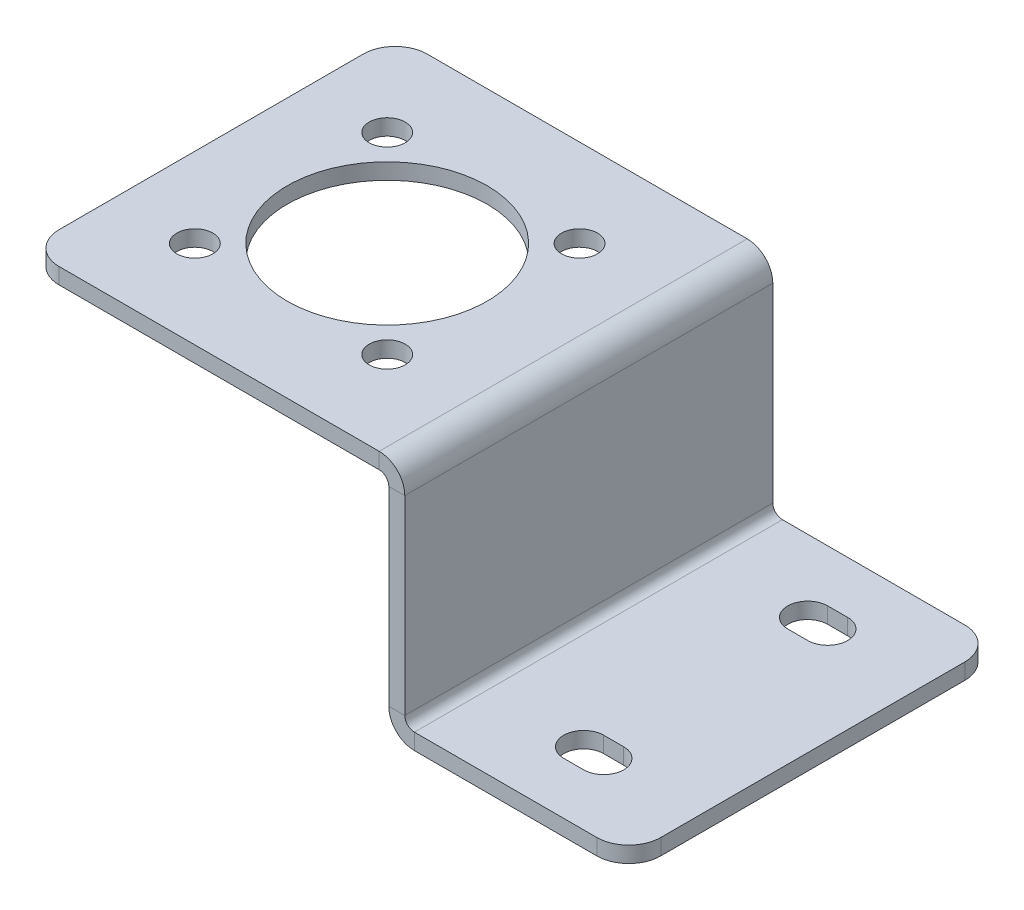
SolidWorks part; units mm, degrees
note: The reader was unsure of these and kept them because the rebuilt part matched: flange length of "Edge-Flange1", "Edge-Flange2".
ref_plane "Front Plane" through (0, 0, 0) normal (0, 0, 1) x (1, 0, 0)
ref_plane "Top Plane" through (0, 0, 0) normal (0, 1, 0) x (1, 0, 0)
ref_plane "Right Plane" through (0, 0, 0) normal (1, 0, 0) x (0, 0, -1)
sketch "Sketch1" plane through (0, 0, 0) normal (0, 1, 0) x (1, 0, 0)
  line L1 (-22, 23) -> (22, 23)
  line L2 (-22, 23) -> (-22, -23)
  line L3 (-22, -23) -> (22, -23)
  line L4 (22, 23) -> (22, -23)
  line L5 (-22, 23) -> (22, -23) construction
  line L6 (-22, -23) -> (22, 23) construction
  circle A0 centre (0, 0) radius 12.5
  circle A1 centre (0, 0) radius 17 construction
  circle A3 centre (12.0208, 12.0208) radius 2.25
  circle A5 centre (12.0208, -12.0208) radius 2.25
  circle A7 centre (-12.0208, -12.0208) radius 2.25
  circle A9 centre (-12.0208, 12.0208) radius 2.25
  point P0 (0, 0)
  point P28 (0, 0)
  dimension "D3" = 34
  dimension "D4" = 4.5
  dimension "D5" = 25
  dimension "D1" = 44
  dimension "D2" = 46
base flange "Base-Flange1" sketch "Sketch1" thickness 2 reverse thickness direction no parameters "D1"=0.7366
edge flange "Edge-Flange1" sketch "Sketch8" flange angle 90 flange length 27 flange position bend outside bend radius 1.2 thickness 2 relief rectangular parameters "D6"=10
sketch "Sketch8" plane through (22, -2, 0) normal (1, 0, 0) x (0, 0, 1)
  line L0 (23, 0) -> (-23, 0) construction
  line L1 (23, 0) -> (-23, 0)
  line L2 (-23, 0) -> (-23, 25)
  line L3 (-23, 25) -> (23, 25)
  line L4 (23, 25) -> (23, 0)
bend "EdgeBend1" bend radius 1.2 bend angle 90 parameters "D5"=1
edge flange "Edge-Flange2" sketch "Sketch11" flange angle 90 flange length 30 flange position bend outside bend radius 1.2 thickness 2 relief rectangular parameters "D6"=10
sketch "Sketch11" plane through (25.2, -27, 0) normal (0, -1, 0) x (0, 0, -1)
  line L0 (-23, 0) -> (23, 0) construction
  line L1 (-23, 0) -> (23, 0)
  line L2 (-23, 0) -> (-23, 28)
  line L3 (-23, 28) -> (23, 28)
  line L4 (23, 28) -> (23, 0)
bend "EdgeBend2" bend radius 1.2 bend angle 90 parameters "D5"=2
sketch "Sketch12" plane through (0, -28.2, 0) normal (0, 1, 0) x (1, 0, 0)
  line L0 (39.8, -23) -> (39.8, 11.5) construction
  line L1 (53.2, -23) -> (26.4, -23) construction
  line L2 (26.4, 23) -> (53.2, 23) construction
  line L3 (38.5619, 16.5) -> (41.0619, 16.5)
  line L4 (38.5619, 11.5) -> (41.0619, 11.5)
  line L5 (38.5619, -16.5) -> (41.0619, -16.5)
  line L6 (38.5619, -11.5) -> (41.0619, -11.5)
  line L7 (39.8, 16.5) -> (39.8, 23) construction
  line L8 (39.8, 11.5) -> (39.8, 16.5) construction
  line L9 (53.2, 0) -> (26.4, 0) construction
  line L10 (53.2, 23) -> (53.2, -23) construction
  line L11 (26.4, -23) -> (26.4, 23) construction
  arc A0 (38.5619, 16.5) -> (38.5619, 11.5) centre (38.5619, 14) ccw
  arc A2 (41.0619, 11.5) -> (41.0619, 16.5) centre (41.0619, 14) ccw
  arc A4 (38.5619, -16.5) -> (38.5619, -11.5) centre (38.5619, -14) cw
  arc A5 (41.0619, -11.5) -> (41.0619, -16.5) centre (41.0619, -14) cw
  dimension "D1" = 9
extrude "Cut-Extrude1" cut sketch "Sketch12" against normal blind 2 contours A0 L4 A2 L3 | A5 L5 A4 L6 normal cut yes
fillet "Fillet1" radius 4 4 edges at (53.2, -29.2, -23) (53.2, -29.2, 23) (-22, -1, -23) (-22, -1, 23)
sketch "Bend-Lines1" [suppressed] plane through (0, 0, 0) normal (0, 1, 0) x (1, 0, 0)
sketch "Bounding-Box1" [suppressed] plane through (0, 0, 0) normal (0, 1, 0) x (1, 0, 0)
sheet metal parameters "Sheet-Metal1" thickness 2 parameters "D1"=0.7366
flat pattern "Flat-Pattern1" [suppressed]
sketch "Bend-Lines2" plane through (0, 0, 0) normal (0, 1, 0) x (1, 0, 0)
sketch3d "Bounding-Box2" [suppressed]
  line L0 (22, 23, 0) -> (22, -23, 0) construction
  line L1 (-22, 23, 0) -> (-22, -23, 0) construction
  line L2 (22, 23, 0) -> (-22, 23, 0) construction
  line L3 (22, -23, 0) -> (-22, -23, 0) construction
sheet metal parameters "Sheet-Metal2" thickness 2 parameters "D1"=0.7366
flat pattern "Flat-Pattern1"
sketch "Bend-Lines2" plane through (0, 0, 0) normal (0, 1, 0) x (1, 0, 0)
  line L0 (23.7279, -23) -> (23.7279, 23) construction
  line L1 (23.7279, -23) -> (23.7279, 23) construction
sketch3d "Bounding-Box2" [suppressed]
  line L0 (49.2558, -23, 0) -> (-22, -23, 0) construction
  line L1 (49.2558, 23, 0) -> (-22, 23, 0) construction
  line L2 (49.2558, -23, 0) -> (49.2558, 23, 0) construction
  line L3 (-22, -23, 0) -> (-22, 23, 0) construction
bend of the flat pattern "Flatten-<EdgeBend1>1"
sheet metal parameters "Sheet-Metal3" thickness 2 parameters "D1"=0.7366
flat pattern "Flat-Pattern1" [suppressed]
sketch "Bend-Lines2" plane through (0, 0, 0) normal (0, 1, 0) x (1, 0, 0)
  line L0 (23.7279, -23) -> (23.7279, 23) construction
  line L1 (23.7279, -23) -> (23.7279, 23) construction
  line L2 (50.9836, -23) -> (50.9836, 23) construction
  line L3 (50.9836, -23) -> (50.9836, 23) construction
sketch3d "Bounding-Box2" [suppressed]
  line L0 (82.7115, -23, 0) -> (-22, -23, 0) construction
  line L1 (82.7115, 23, 0) -> (-22, 23, 0) construction
  line L2 (82.7115, -23, 0) -> (82.7115, 23, 0) construction
  line L3 (-22, -23, 0) -> (-22, 23, 0) construction
bend of the flat pattern "Flatten-<EdgeBend1>1"
bend of the flat pattern "Flatten-<EdgeBend2>1"
sketch "Sketch12-1" [suppressed] plane through (26.3115, 0, 0) normal (0, 1, 0) x (1, 0, 0)
  line L0 (41.4, -23) -> (41.4, 23) construction
sheet metal parameters "Sheet-Metal4" thickness 2 parameters "D1"=0.7366
flat pattern "Flat-Pattern1" [suppressed]
sketch "Bend-Lines2" plane through (0, 0, 0) normal (0, 1, 0) x (1, 0, 0)
  line L0 (23.7279, -23) -> (23.7279, 23) construction
  line L1 (23.7279, -23) -> (23.7279, 23) construction
  line L2 (50.9836, -23) -> (50.9836, 23) construction
  line L3 (50.9836, -23) -> (50.9836, 23) construction
sketch3d "Bounding-Box2" [suppressed]
  line L0 (-22, -22.9999, 0) -> (79.5115, -23, 0) construction
  line L1 (-22, 23, 0) -> (79.5115, 22.9999, 0) construction
  line L2 (-22, -22.9999, 0) -> (-22, 23, 0) construction
  line L3 (79.5115, -23, 0) -> (79.5115, 22.9999, 0) construction
bend of the flat pattern "Flatten-<EdgeBend1>1"
bend of the flat pattern "Flatten-<EdgeBend2>1"
sketch "Sketch12-1" plane through (26.3115, 0, 0) normal (0, 1, 0) x (1, 0, 0)
  line L0 (39.8, -23) -> (39.8, 11.5) construction
  line L3 (38.5619, 16.5) -> (41.0619, 16.5)
  line L4 (38.5619, 11.5) -> (41.0619, 11.5)
  line L5 (38.5619, -16.5) -> (41.0619, -16.5)
  line L6 (38.5619, -11.5) -> (41.0619, -11.5)
  line L7 (39.8, 16.5) -> (39.8, 23) construction
  line L8 (39.8, 11.5) -> (39.8, 16.5) construction
  line L9 (53.2, 0) -> (26.4, 0) construction
  arc A0 (38.5619, 16.5) -> (38.5619, 11.5) centre (38.5619, 14) ccw
  arc A2 (41.0619, 11.5) -> (41.0619, 16.5) centre (41.0619, 14) ccw
  arc A4 (38.5619, -16.5) -> (38.5619, -11.5) centre (38.5619, -14) cw
  arc A5 (41.0619, -11.5) -> (41.0619, -16.5) centre (41.0619, -14) cw
  dimension "D1" = 9
